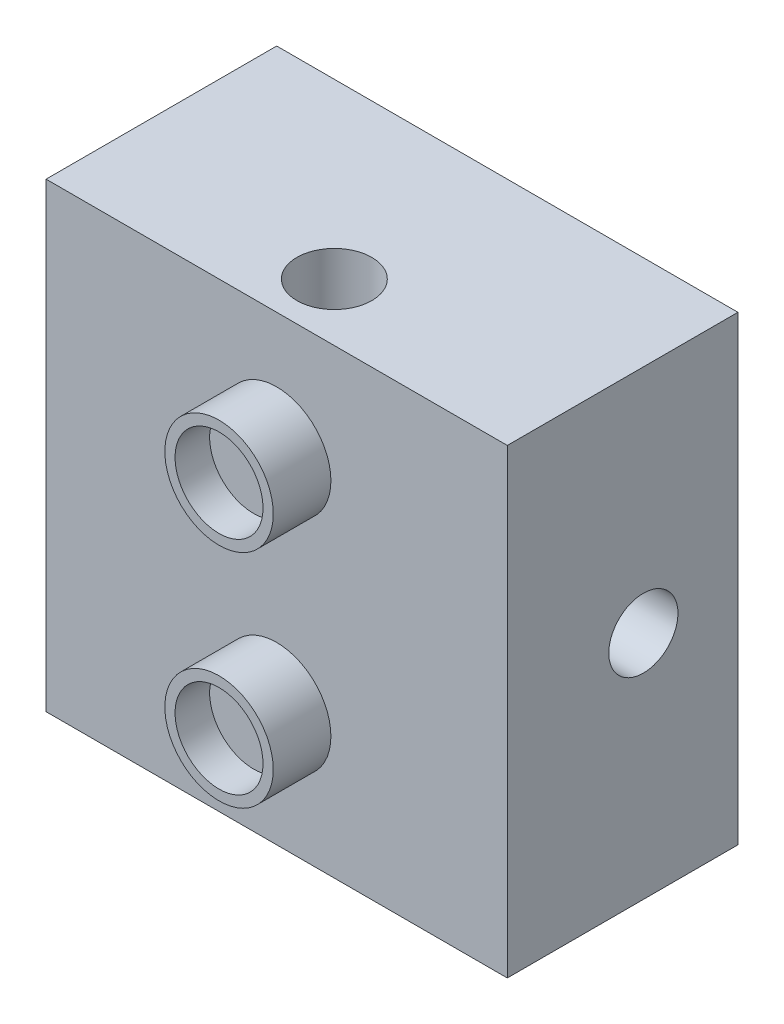
SolidWorks part; units mm, degrees
ref_plane "Front Plane" through (0, 0, 0) normal (0, 0, 1) x (1, 0, 0)
ref_plane "Top Plane" through (0, 0, 0) normal (0, 1, 0) x (1, 0, 0)
ref_plane "Right Plane" through (0, 0, 0) normal (1, 0, 0) x (0, 0, -1)
sketch "Sketch1" plane through (0, 0, 0) normal (0, 0, 1) x (1, 0, 0)
  line L1 (-50.8, 50.8) -> (50.8, 50.8)
  line L2 (-50.8, 50.8) -> (-50.8, -50.8)
  line L3 (-50.8, -50.8) -> (50.8, -50.8)
  line L4 (50.8, 50.8) -> (50.8, -50.8)
  line L5 (-50.8, 50.8) -> (50.8, -50.8) construction
  line L6 (-50.8, -50.8) -> (50.8, 50.8) construction
  point P0 (0, 0)
  dimension "D1" = 101.6
  dimension "D2" = 101.6
extrude "Boss-Extrude1" add sketch "Sketch1" along normal blind 50.8
sketch "Sketch2" plane through (0, 50.8, 0) normal (0, 1, 0) x (1, 0, 0)
  line L0 (50.8, -50.8) -> (-50.8, -50.8) construction
  circle A0 centre (0, -38.1) radius 8.255
  dimension "D1" = 16.51
  dimension "D2" = 12.7
extrude "Cut-Extrude1" cut sketch "Sketch2" against normal blind 254
sketch "Sketch3" plane through (50.8, 0, 0) normal (1, 0, 0) x (0, 0, -1)
  line L2 (-50.8, -50.8) -> (-50.8, 50.8) construction
  circle A0 centre (-20.828, 0) radius 7.62
  dimension "D1" = 15.24
  dimension "D2" = 29.972
extrude "Cut-Extrude2" cut sketch "Sketch3" against normal blind 254
sketch "Sketch4" plane through (0, 0, 50.8) normal (0, 0, 1) x (1, 0, 0)
  circle A0 centre (0, 24.639) radius 11.9414
  circle A1 centre (0, -24.1238) radius 11.9414
extrude "Boss-Extrude2" add sketch "Sketch4" along normal blind 12.7
sketch "Sketch5" plane through (0, 0, 63.5) normal (0, 0, 1) x (1, 0, 0)
  circle A0 centre (0, 24.639) radius 9.6887
  circle A1 centre (0, -24.1238) radius 9.6887
extrude "Cut-Extrude3" cut sketch "Sketch5" against normal blind 7.62
